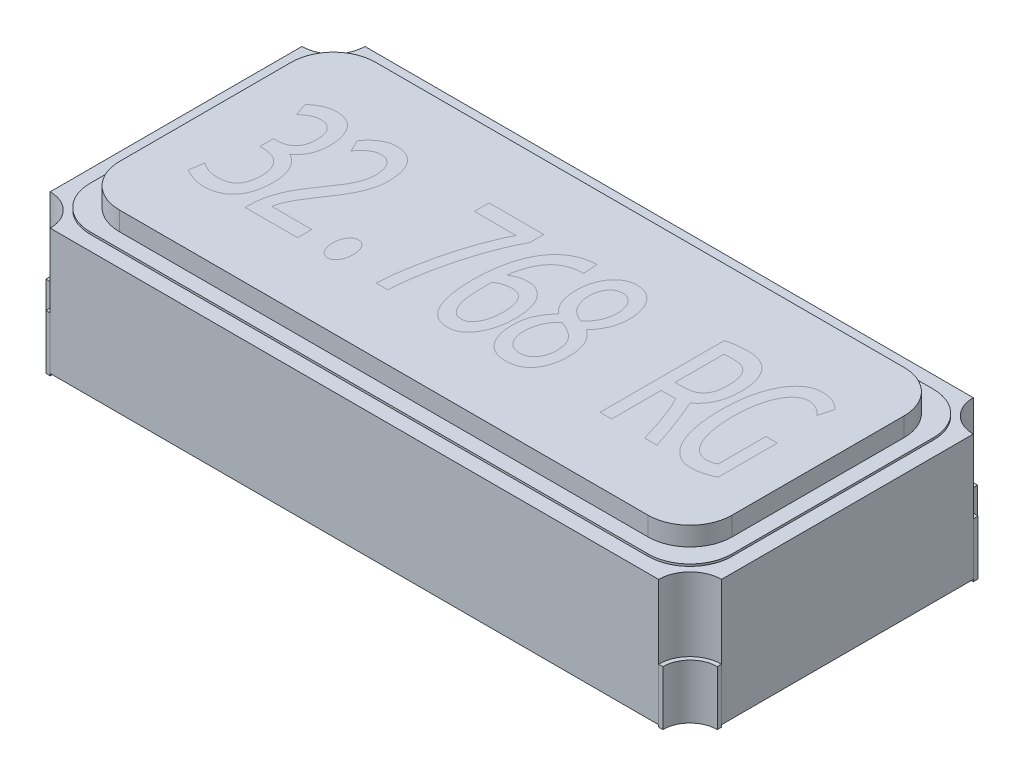
SolidWorks part; units mm, degrees
ref_plane "Спереди" through (0, 0, 0) normal (0, 0, 1) x (1, 0, 0)
ref_plane "Сверху" through (0, 0, 0) normal (0, 1, 0) x (1, 0, 0)
ref_plane "Справа" through (0, 0, 0) normal (1, 0, 0) x (0, 0, -1)
ref_plane "Plane1" through (0, 0.01, 0) normal (0, 1, 0) x (1, 0, 0)
sketch "Sketch1" plane through (0, 0, 0) normal (0, 1, 0) x (1, 0, 0)
  line L1 (-1.45, 0.75) -> (1.45, 0.75)
  line L2 (-1.6, 0.6) -> (-1.6, -0.6)
  line L3 (-1.45, -0.75) -> (1.45, -0.75)
  line L4 (1.6, 0.6) -> (1.6, -0.6)
  arc A0 (-1.6, 0.6) -> (-1.45, 0.75) centre (-1.6, 0.75) ccw
  arc A1 (-1.45, -0.75) -> (-1.6, -0.6) centre (-1.6, -0.75) ccw
  arc A2 (1.45, 0.75) -> (1.6, 0.6) centre (1.6, 0.75) ccw
  arc A3 (1.6, -0.6) -> (1.45, -0.75) centre (1.6, -0.75) ccw
  dimension "D1" = 1.5
  dimension "D2" = 3.2
  dimension "D3" = 0.75
  dimension "D4" = 1.6
extrude "Boss-Extrude1" add sketch "Sketch1" along normal blind 0.6 from surface starting at plane "Plane1"
sketch "Sketch3" plane through (0, 0.61, 0) normal (0, 1, 0) x (1, 0, 0)
  line L0 (-1.6, 0.6) -> (-1.6, -0.6) construction
  line L1 (-1.33, 0.68) -> (1.33, 0.68)
  line L2 (-1.53, 0.48) -> (-1.53, -0.48)
  line L3 (-1.33, -0.68) -> (1.33, -0.68)
  line L4 (1.53, 0.48) -> (1.53, -0.48)
  line L5 (1.45, 0.75) -> (-1.45, 0.75) construction
  line L6 (1.6, -0.6) -> (1.6, 0.6) construction
  line L7 (-1.45, -0.75) -> (1.45, -0.75) construction
  arc A0 (1.33, 0.68) -> (1.53, 0.48) centre (1.33, 0.48) cw
  arc A1 (1.33, -0.68) -> (1.53, -0.48) centre (1.33, -0.48) ccw
  arc A2 (-1.53, -0.48) -> (-1.33, -0.68) centre (-1.33, -0.48) ccw
  arc A3 (-1.33, 0.68) -> (-1.53, 0.48) centre (-1.33, 0.48) ccw
  arc A4 (1.33, -0.68) -> (1.53, -0.48) centre (1.33, -0.48) ccw
  arc A5 (1.33, -0.68) -> (1.53, -0.48) centre (1.33, -0.48) ccw
  arc A6 (1.33, -0.68) -> (1.53, -0.48) centre (1.33, -0.48) ccw
  arc A7 (1.33, -0.68) -> (1.53, -0.48) centre (1.33, -0.48) ccw
  arc A8 (1.33, -0.68) -> (1.53, -0.48) centre (1.33, -0.48) ccw
  arc A9 (1.33, -0.68) -> (1.53, -0.48) centre (1.33, -0.48) ccw
  arc A10 (1.33, -0.68) -> (1.53, -0.48) centre (1.33, -0.48) ccw
  dimension "D5" = 0.2
  dimension "D6" = 0.2
  dimension "D7" = 0.2
  dimension "D8" = 0.2
  dimension "D9" = 0.2
  dimension "D10" = 0.2
  dimension "D11" = 0.2
  dimension "D12" = 0.2
  dimension "D1" = 0.07
  dimension "D2" = 0.07
  dimension "D3" = 0.07
  dimension "D4" = 0.07
extrude "Boss-Extrude2" add sketch "Sketch3" along normal blind 0.01 contours L1 A3 L2 A2 L3 A1 L4 A0 region at (0, 0.61, 0)
sketch "Sketch5" plane through (0, 0.62, 0) normal (0, 1, 0) x (1, 0, 0)
  line L0 (-1.33, 0.68) -> (1.33, 0.68) construction
  line L1 (-1.26, 0.61) -> (1.26, 0.61)
  line L2 (-1.46, 0.41) -> (-1.46, -0.41)
  line L3 (-1.26, -0.61) -> (1.26, -0.61)
  line L4 (1.46, 0.41) -> (1.46, -0.41)
  line L5 (-1.53, 0.48) -> (-1.53, -0.48) construction
  line L6 (-1.33, -0.68) -> (1.33, -0.68) construction
  line L7 (1.53, 0.48) -> (1.53, -0.48) construction
  arc A0 (1.26, 0.61) -> (1.46, 0.41) centre (1.26, 0.41) cw
  arc A1 (1.26, -0.61) -> (1.46, -0.41) centre (1.26, -0.41) ccw
  arc A2 (-1.46, -0.41) -> (-1.26, -0.61) centre (-1.26, -0.41) ccw
  arc A3 (-1.26, 0.61) -> (-1.46, 0.41) centre (-1.26, 0.41) ccw
  dimension "D5" = 0.2
  dimension "D1" = 0.07
  dimension "D2" = 0.07
  dimension "D3" = 0.07
  dimension "D4" = 0.07
extrude "Boss-Extrude3" add sketch "Sketch5" along normal blind 0.09
sketch "Sketch7" plane through (0, 0.01, 0) normal (0, -1, 0) x (1, 0, 0)
  line L0 (0, 0.9753) -> (0, -1.5091) construction
  line L1 (-0.85, 0.7) -> (-1.45, 0.7)
  line L2 (-0.85, 0.7) -> (-0.85, -0.7)
  line L3 (-0.85, -0.7) -> (-1.45, -0.7)
  line L4 (-1.55, 0.6) -> (-1.55, -0.6)
  line L5 (-1.6, 0.6) -> (-1.6, -0.6) construction
  line L6 (1.45, 0.75) -> (-1.45, 0.75) construction
  line L7 (-1.45, -0.75) -> (1.45, -0.75) construction
  line L8 (-1.45, 0.75) -> (-1.45, 0.7)
  line L9 (-1.45, 0.75) -> (-1.4699, 0.75)
  line L10 (-1.6, 0.6) -> (-1.5999, 0.62)
  line L11 (-1.6, 0.6) -> (-1.55, 0.6)
  line L12 (-1.45, -0.75) -> (-1.45, -0.7)
  line L13 (-1.45, -0.75) -> (-1.47, -0.75)
  line L14 (-1.6, -0.6) -> (-1.6, -0.6225)
  line L15 (-1.6, -0.6) -> (-1.55, -0.6)
  line L16 (1.6, -0.6) -> (1.55, -0.6)
  line L17 (1.6, -0.6) -> (1.6, -0.6225)
  line L18 (1.45, -0.75) -> (1.47, -0.75)
  line L19 (1.45, -0.75) -> (1.45, -0.7)
  line L20 (1.6, 0.6) -> (1.55, 0.6)
  line L21 (1.6, 0.6) -> (1.5999, 0.62)
  line L22 (1.45, 0.75) -> (1.4699, 0.75)
  line L23 (1.45, 0.75) -> (1.45, 0.7)
  line L24 (1.55, 0.6) -> (1.55, -0.6)
  line L25 (0.85, -0.7) -> (1.45, -0.7)
  line L26 (0.85, 0.45) -> (0.85, -0.7)
  line L27 (1.1, 0.7) -> (1.45, 0.7)
  line L28 (1.1, 0.7) -> (0.85, 0.45)
  arc A0 (-1.5999, 0.62) -> (-1.4699, 0.75) centre (-1.5999, 0.75) ccw
  arc A1 (-1.47, -0.75) -> (-1.6, -0.6225) centre (-1.6, -0.7525) ccw
  arc A2 (1.47, -0.75) -> (1.6, -0.6225) centre (1.6, -0.7525) cw
  arc A3 (1.5999, 0.62) -> (1.4699, 0.75) centre (1.5999, 0.75) cw
  point P44 (0.85, 0.7)
  dimension "D1" = 0.75
  dimension "D2" = 0.05
  dimension "D3" = 0.05
  dimension "D4" = 0.05
extrude "Boss-Extrude4" add sketch "Sketch7" against normal blind 0.25 and the other way blind 0.01 separate body
sketch "Sketch10" plane through (0, 0.71, 0) normal (0, 1, 0) x (1, 0, 0)
  line L0 (-1.3, -0.3) -> (1.3, -0.3) construction
  text T0 "32.768 RG" font "Ubuntu Mono" height 0.6
  dimension "D1" = 2.6
  dimension "D2" = 1.3
  dimension "D3" = 0.3
wrap "Wrap2" sketch "Sketch10" wrap type scribe source sketch "Sketch10" face at (0, 0.71, 0)
equation "\"D3@Sketch1\"=\"D1@Sketch1\"/2"
equation "\"D4@Sketch1\"=\"D2@Sketch1\"/2"
equation "\"D2@Sketch10\"=\"D1@Sketch10\"/2"
